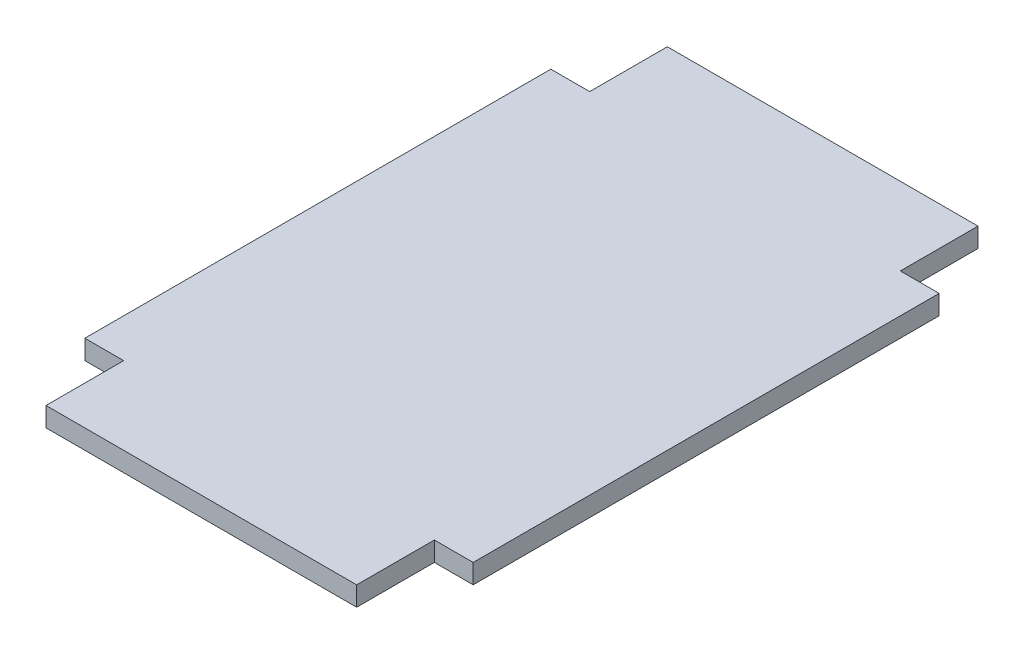
SolidWorks part; units mm, degrees
material "Oak"
ref_plane "Front Plane" through (0, 0, 0) normal (0, 0, 1) x (1, 0, 0)
ref_plane "Top Plane" through (0, 0, 0) normal (0, 1, 0) x (1, 0, 0)
ref_plane "Right Plane" through (0, 0, 0) normal (1, 0, 0) x (0, 0, -1)
sketch "Sketch1" plane through (0, 0, 0) normal (0, 1, 0) x (1, 0, 0)
  line L0 (-194.7505, 337.1161) -> (-194.7505, -120.0839)
  line L1 (-194.7505, -120.0839) -> (-156.6505, -120.0839)
  line L2 (-156.6505, -120.0839) -> (-156.6505, -196.2839)
  line L3 (-156.6505, -196.2839) -> (148.1495, -196.2839)
  line L4 (148.1495, -196.2839) -> (148.1495, -120.0839)
  line L5 (148.1495, -120.0839) -> (186.2495, -120.0839)
  line L6 (186.2495, -120.0839) -> (186.2495, 337.1161)
  line L7 (186.2495, 337.1161) -> (148.1495, 337.1161)
  line L8 (148.1495, 337.1161) -> (148.1495, 413.3161)
  line L9 (148.1495, 413.3161) -> (-156.6505, 413.3161)
  line L10 (-156.6505, 413.3161) -> (-156.6505, 337.1161)
  line L11 (-156.6505, 337.1161) -> (-194.7505, 337.1161)
  dimension "D1" = 609.6
  dimension "D2" = 304.8
  dimension "D3" = 304.8
  dimension "D4" = 38.1
  dimension "D5" = 38.1
  dimension "D6" = 38.1
  dimension "D7" = 76.2
  dimension "D8" = 76.2
  dimension "D9" = 76.2
  dimension "D10" = 76.2
extrude "Boss-Extrude1" add sketch "Sketch1" along normal blind 19.05
